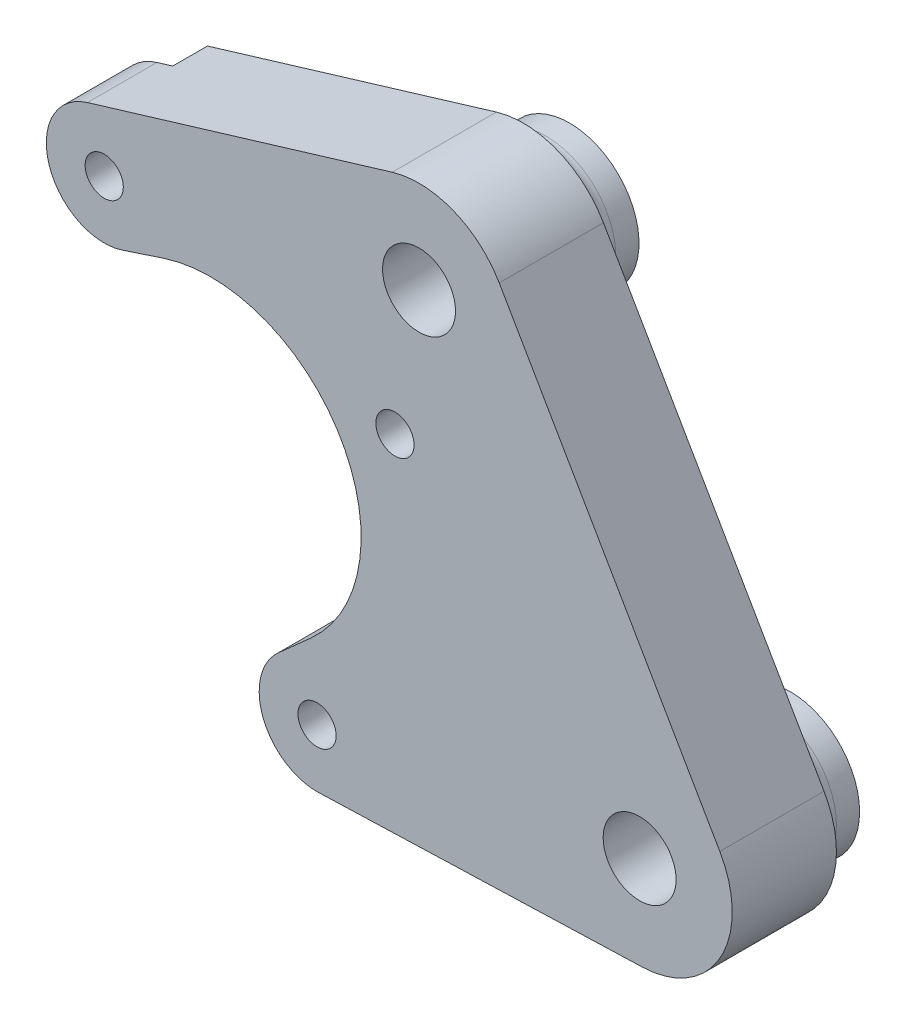
SolidWorks part; units mm, degrees
ref_plane "Front Plane" through (0, 0, 0) normal (0, 0, 1) x (1, 0, 0)
ref_plane "Top Plane" through (0, 0, 0) normal (0, 1, 0) x (1, 0, 0)
ref_plane "Right Plane" through (0, 0, 0) normal (1, 0, 0) x (0, 0, -1)
sketch "Sketch1" plane through (0, 0, 0) normal (0, 0, 1) x (1, 0, 0)
  line L0 (18, 21) -> (37.0525, -11.9999) construction
  line L1 (15.9217, 9.1924) -> (-9.1924, 15.9217) construction
  line L2 (-9.1924, 15.9217) -> (-15.9217, -9.1924) construction
  line L3 (-15.9217, -9.1924) -> (9.1924, -15.9217) construction
  line L4 (9.1924, -15.9217) -> (15.9217, 9.1924) construction
  line L5 (0, 0) -> (50.7667, 0) construction
  line L6 (0, 0) -> (-9.1924, 15.9217) construction
  line L7 (-4.0727, 12.3456) -> (-7.626, 11.1734)
  line L8 (8.6552, -9.6998) -> (5.8634, -12.191)
  line L9 (0, 0) -> (9.1924, -15.9217) construction
  line L10 (15.6872, 28.6584) -> (-10.6379, 20.7082)
  line L11 (24.9282, 25) -> (43.9807, -7.9999)
  line L12 (37.3166, -19.9955) -> (9.3574, -20.919)
  arc A0 (8.6552, -9.6998) -> (-4.0727, 12.3456) centre (0, 0) ccw
  circle A1 centre (18, 21) radius 3.15
  circle A2 centre (-9.1924, 15.9217) radius 1.65
  circle A3 centre (15.9217, 9.1924) radius 1.65
  circle A4 centre (9.1924, -15.9217) radius 1.65
  circle A6 centre (37.0525, -11.9999) radius 3.15
  arc A7 (-10.6379, 20.7082) -> (-7.626, 11.1734) centre (-9.1924, 15.9217) ccw
  arc A8 (24.9282, 25) -> (15.6872, 28.6584) centre (18, 21) ccw
  arc A9 (37.3166, -19.9955) -> (43.9807, -7.9999) centre (37.0525, -11.9999) ccw
  arc A10 (5.8634, -12.191) -> (9.3574, -20.919) centre (9.1924, -15.9217) ccw
  dimension "D1" = 26
  dimension "D2" = 3.3
  dimension "D3" = 6.3
  dimension "D9" = 5
  dimension "D10" = 8
  dimension "D4" = 21
  dimension "D5" = 38.105
  dimension "D6" = 60
  dimension "D7" = 18
  dimension "D8" = 15
extrude "Boss-Extrude1" add sketch "Sketch1" along normal blind 9
sketch "Sketch2" plane through (0, 0, 0) normal (0, 0, -1) x (-1, 0, 0)
  line L0 (-9.1924, -15.9217) -> (-15.9217, 9.1924) construction
  line L1 (10.7961, 21.5278) -> (-20.1136, 13.2456)
  line L2 (-21.5278, 10.7961) -> (-13.2456, -20.1136)
  line L5 (-20.1136, 13.2456) -> (-21.5278, 10.7961)
  line L6 (23.2164, 14.3569) -> (10.7961, 21.5278)
  line L8 (-13.2456, -20.1136) -> (8.7791, -32.8295)
  line L9 (23.2164, 14.3569) -> (8.7791, -32.8295)
  line L11 (20.7057, -7.7281) -> (13.9247, 17.5792) [skipped]
  line L12 (-7.7281, -20.7057) -> (17.5792, -13.9247) [skipped]
  circle A0 centre (0, 0) radius 18 construction
  circle A1 centre (0, 0) radius 24.0416 construction
  circle A2 centre (-18, 21) radius 6 construction
  circle A3 centre (-18, 21) radius 3.15 construction
  point P2 (6.5153, 24.3153)
  point P3 (-22.0454, 12.7279)
  point P4 (-6.5153, -24.3153)
  point P5 (24.3153, -6.5153)
  dimension "D1" = 36
  dimension "D2" = 12
  dimension "D4" = 2
extrude "Cut-Extrude1" cut sketch "Sketch2" against normal offset from surface (3 mm away) 6 up to face at (21.15, 21, 9)
sketch "Sketch3" plane through (0, 0, 0) normal (0, 0, -1) x (-1, 0, 0)
  circle A0 centre (-18, 21) radius 6
  circle A1 centre (-18, 21) radius 3.15
  circle A2 centre (-37.0525, -11.9999) radius 3.15
  circle A3 centre (-37.0525, -11.9999) radius 6
  dimension "D1" = 12
extrude "Boss-Extrude2" add sketch "Sketch3" along normal blind 4
fillet "Fillet1" radius 2 2 edges at (24, 21, 0) (43.0525, -11.9999, 0)
